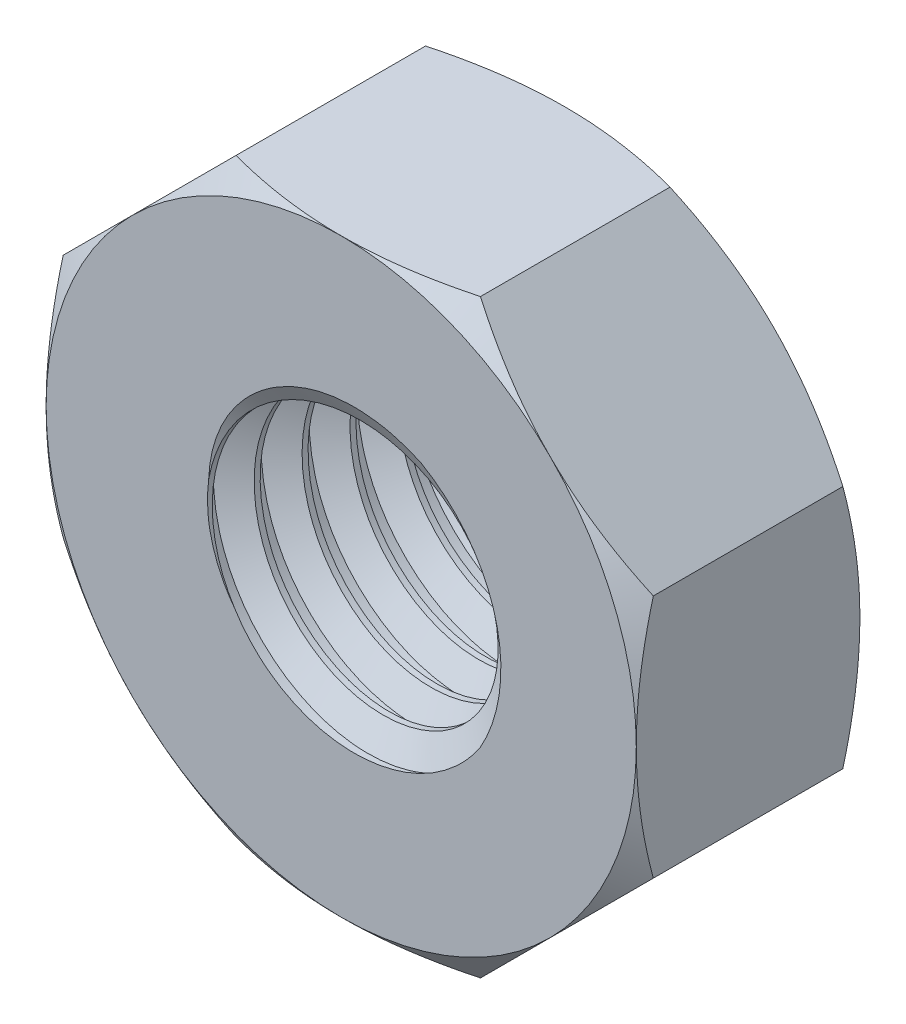
SolidWorks part; units mm, degrees
material "Galvanized Steel"
ref_plane "Przednia" through (0, 0, 0) normal (0, 0, 1) x (1, 0, 0)
ref_plane "Górna" through (0, 0, 0) normal (0, 1, 0) x (1, 0, 0)
ref_plane "Prawa" through (0, 0, 0) normal (1, 0, 0) x (0, 0, -1)
sketch "Sketch2" plane through (0, 0, 0) normal (0, 0, 1) x (1, 0, 0)
  line L0 (-10.8197, 2.2363) -> (27.0105, 2.2363) construction
  line L1 (3.8268, 9.2388) -> (-3.8268, 9.2388)
  line L2 (-3.8268, 9.2388) -> (-9.2388, 3.8268)
  line L3 (-9.2388, 3.8268) -> (-9.2388, -3.8268)
  line L4 (-9.2388, -3.8268) -> (-3.8268, -9.2388)
  line L5 (-3.8268, -9.2388) -> (3.8268, -9.2388)
  line L6 (3.8268, -9.2388) -> (9.2388, -3.8268)
  line L7 (9.2388, -3.8268) -> (9.2388, 3.8268)
  line L8 (9.2388, 3.8268) -> (3.8268, 9.2388)
  circle A0 centre (0, 0) radius 5
  circle A1 centre (0, 0) radius 9.2388 construction
  dimension "D1" = 10
  dimension "D2" = 10
extrude "Boss-Extrude1" add sketch "Sketch2" along normal mid plane 7
thread "Thread3" pitch 1.5 method extrude trim with start face yes trim with end face yes profile "Thread Profile3" start angle 0, offset 2, length 0, pitch 1.5, diameter 10
ref_plane "Plane3" through (-5, 0, 5.5) normal (0, 1, 0) x (1, 0, 0)
sketch "Thread Profile3" plane through (-5, 0, 5.5) normal (0, 1, 0) x (1, 0, 0)
  line L0 (0, 0) -> (0, 1.5) construction
  line L1 (0, 0) -> (0.8119, 0.4687)
  line L2 (0.8119, 0.4687) -> (0.8119, 0.6562)
  line L3 (0.8119, 0.6562) -> (0, 1.125)
  line L4 (0.8119, 0.5625) -> (0, 0.5625) construction
  line L11 (0, 0) -> (0, 1.125)
  point P2 (0, 0)
  dimension "Pitch" = 1.5
  dimension "Profile_Angle" = 60
  dimension "Profile_Land" = 0.1875
  dimension "Profile_Height" = 0.8119
sketch "Sketch5" plane through (0, 0, 0) normal (1, 0, 0) x (0, 0, -1)
  line L0 (-3.5, 9.2388) -> (-3.5, 11.2388)
  line L1 (-3.5, 11.2388) -> (-2.0996, 11.2388)
  line L2 (-2.0996, 11.2388) -> (-3.5, 9.2388)
  line L3 (-5.7628, 0) -> (8.7458, 0) construction
  line L4 (0, -2.5132) -> (0, 12.9421) construction
  line L5 (2.0996, 11.2388) -> (3.5, 9.2388)
  line L6 (3.5, 11.2388) -> (2.0996, 11.2388)
  line L7 (3.5, 9.2388) -> (3.5, 11.2388)
  dimension "D1" = 2
  dimension "D2" = 35
revolve "Cut-Revolve3" cut sketch "Sketch5" angle 360 about L3
